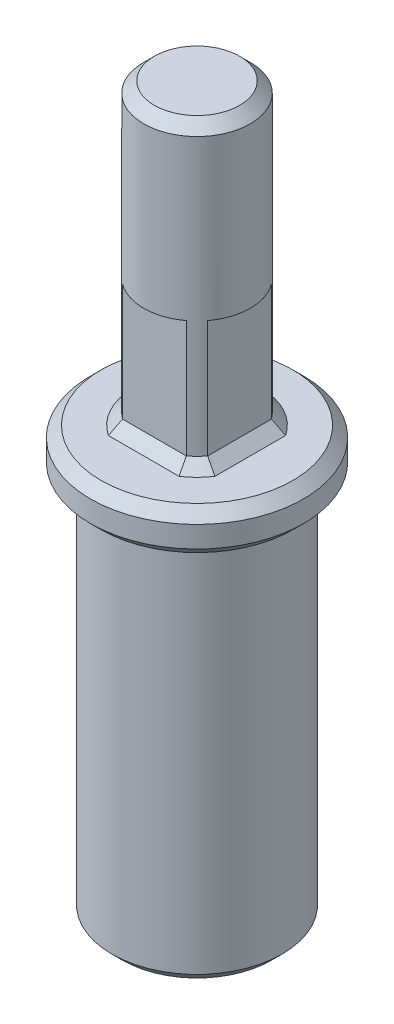
SolidWorks part; units mm, degrees
ref_plane "Front Plane" through (0, 0, 0) normal (0, 0, 1) x (1, 0, 0)
ref_plane "Top Plane" through (0, 0, 0) normal (0, 1, 0) x (1, 0, 0)
ref_plane "Right Plane" through (0, 0, 0) normal (1, 0, 0) x (0, 0, -1)
sketch "Sketch1" plane through (0, 0, 0) normal (0, 1, 0) x (1, 0, 0)
  circle A0 centre (0, 0) radius 4
  dimension "D1" = 8
extrude "Boss-Extrude1" add sketch "Sketch1" along normal blind 18
sketch "Sketch2" plane through (0, 18, 0) normal (0, 1, 0) x (1, 0, 0)
  circle A0 centre (0, 0) radius 5
  dimension "D1" = 10
extrude "Boss-Extrude2" add sketch "Sketch2" along normal blind 2
sketch "Sketch3" plane through (0, 20, 0) normal (0, 1, 0) x (1, 0, 0)
  circle A0 centre (0, 0) radius 2.5
  dimension "D1" = 5
extrude "Boss-Extrude3" add sketch "Sketch3" along normal blind 14
sketch "Sketch4" plane through (0, 34, 0) normal (0, 1, 0) x (1, 0, 0)
  line L0 (-1.5, -2) -> (1.5, -2)
  line L1 (2, 1.5) -> (2, -1.5)
  circle A0 centre (0, 0) radius 2.5 construction
  circle A1 centre (0, 0) radius 2.5 construction
  arc A2 (-1.5, -2) -> (1.5, -2) centre (0, 0) ccw
  arc A3 (2, -1.5) -> (2, 1.5) centre (0, 0) ccw
  point P10 (2, 1.5)
  dimension "D1" = 3
  dimension "D2" = 3
extrude "Cut-Extrude1" cut sketch "Sketch4" against normal up to surface (14 mm away) from offset 8 up to face at (0, 20, 2.5) offset against normal yes
chamfer "Chamfer1" distance 0.5 angle 45 8 edges at (0, 34, 2.5) (0, 0, 4) (0, 20, 5) (2, 20, 0) (-1.7678, 20, -1.7678) (0, 20, 2) (1.7678, 20, 1.7678) (0, 18, 5)
equation "\"D2@Sketch4\"=\"D1@Sketch4\""
